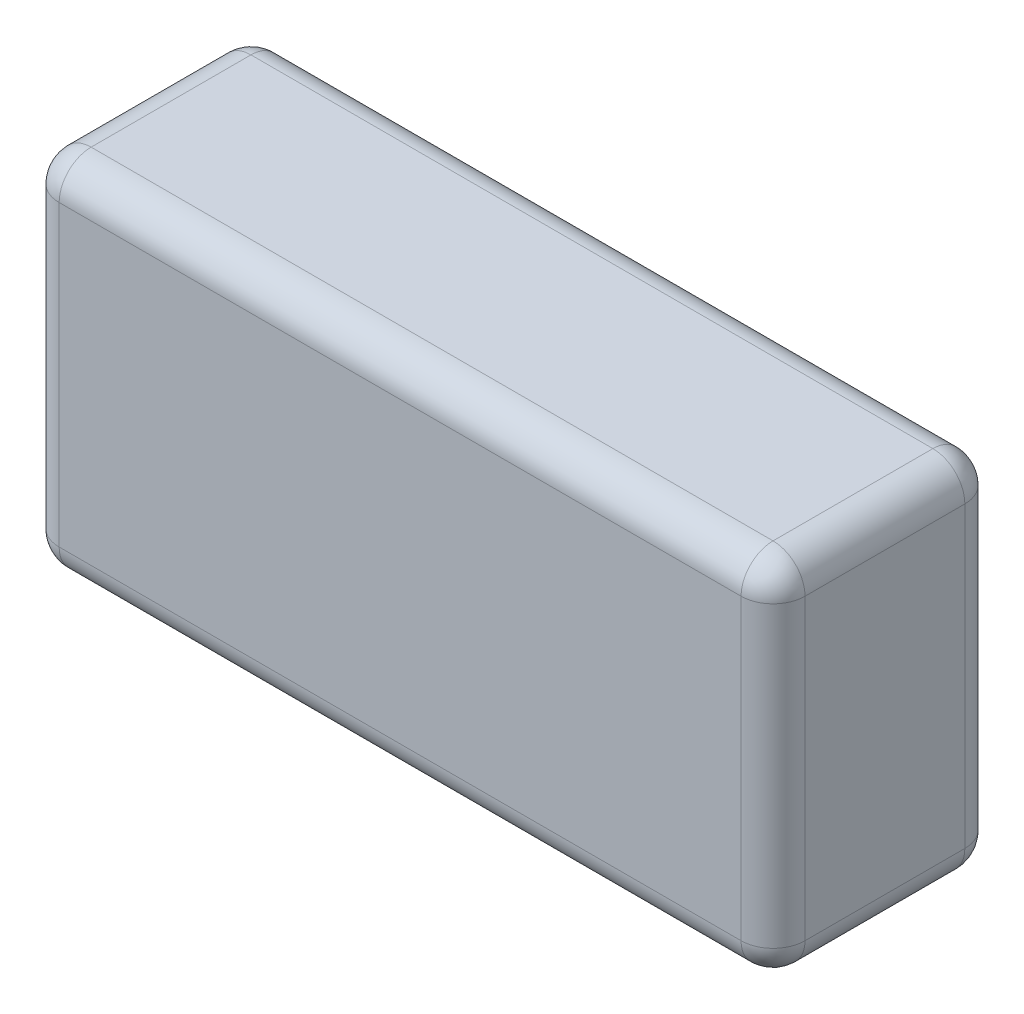
SolidWorks part; units mm, degrees
ref_plane "前视基准面" through (0, 0, 0) normal (0, 0, 1) x (1, 0, 0)
ref_plane "上视基准面" through (0, 0, 0) normal (0, 1, 0) x (1, 0, 0)
ref_plane "右视基准面" through (0, 0, 0) normal (1, 0, 0) x (0, 0, -1)
sketch "草图1" plane through (0, 0, 0) normal (0, 1, 0) x (1, 0, 0)
  line L1 (35, -10.5) -> (-35, -10.5)
  line L2 (35, -10.5) -> (35, 10.5)
  line L3 (35, 10.5) -> (-35, 10.5)
  line L4 (-35, -10.5) -> (-35, 10.5)
  line L5 (35, -10.5) -> (-35, 10.5) construction
  line L6 (35, 10.5) -> (-35, -10.5) construction
  point P0 (0, 0)
  point P6 (0, 0)
extrude "凸台-拉伸1" add sketch "草图1" along normal mid plane 34
fillet "圆角1" radius 3 12 edges at (-35, 0, -10.5) (0, -17, -10.5) (35, 0, -10.5) (35, -17, 0) (-35, 0, 10.5) (35, 0, 10.5) (0, -17, 10.5) (0, 17, -10.5) (35, 17, 0) (0, 17, 10.5) (-35, 17, 0) (-35, -17, 0)
